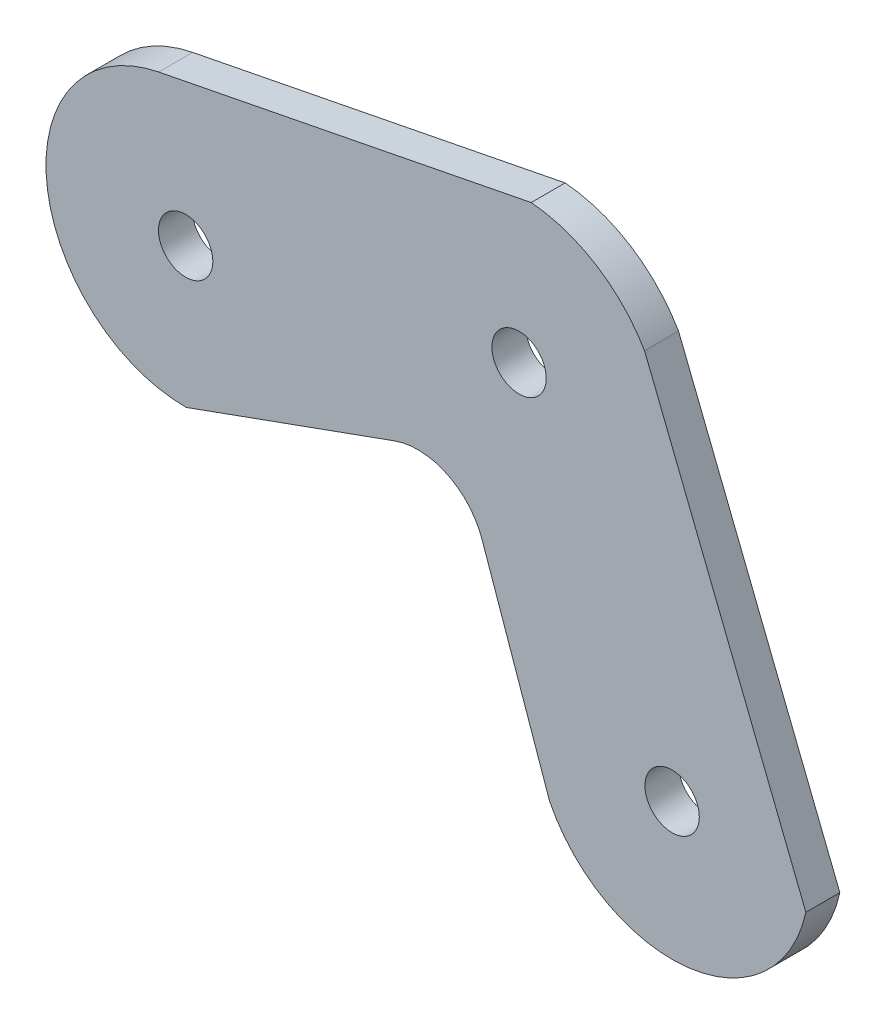
SolidWorks part; units mm, degrees
ref_plane "前视基准面" through (0, 0, 0) normal (0, 0, 1) x (1, 0, 0)
ref_plane "上视基准面" through (0, 0, 0) normal (0, 1, 0) x (1, 0, 0)
ref_plane "右视基准面" through (0, 0, 0) normal (1, 0, 0) x (0, 0, -1)
sketch "草图1" plane through (0, 0, 0) normal (0, 0, 1) x (1, 0, 0)
  line L0 (36.083, 65) -> (85.1444, 74.6422)
  line L1 (85.1444, 74.6422) -> (107.6628, 30)
  line L2 (107.6628, 30) -> (36.083, 65)
  line L3 (0, 0) -> (0, 252.2874)
  line L4 (0, 0) -> (398.1835, 0)
  line L5 (0, 0) -> (50, 0)
  line L6 (50, 0) -> (50, -60.1662)
  line L7 (32.1201, 85.1637) -> (86.9275, 95.9352)
  line L8 (103.6094, 85.3947) -> (127.3443, 25.7012)
  line L9 (36.1784, 44.4508) -> (66.8528, 55.5221)
  line L10 (79.6864, 49.4192) -> (89.6144, 21.0504)
  circle A0 centre (107.6628, 30) radius 4
  circle A1 centre (85.1444, 74.6422) radius 4
  circle A2 centre (36.083, 65) radius 4
  arc A3 (32.1201, 85.1637) -> (36.1784, 44.4508) centre (36.083, 65) ccw
  arc A4 (103.6094, 85.3947) -> (86.9275, 95.9352) centre (85.1444, 74.6422) ccw
  arc A5 (89.6144, 21.0504) -> (127.3443, 25.7012) centre (107.6628, 30) ccw
  arc A6 (66.8528, 55.5221) -> (79.6864, 49.4192) centre (70.2477, 46.116) cw
  point P2 (0, 0)
  dimension "D2" = 50
  dimension "D7" = 10
  dimension "D1" = 30
  dimension "D3" = 50
  dimension "D4" = 50
  dimension "D5" = 65
  dimension "D6" = 65
extrude "凸台-拉伸1" add sketch "草图1" along normal blind 5 contours L10 A5 L8 A4 L7 A3 L9 L2 A2 L0 A1 L1 A0 | L9 A6 L10 L2 A0 L1 A1 L0 A2 region at (30.7178, 65.7034, 0) region at (76.6766, 57.1031, 0)
